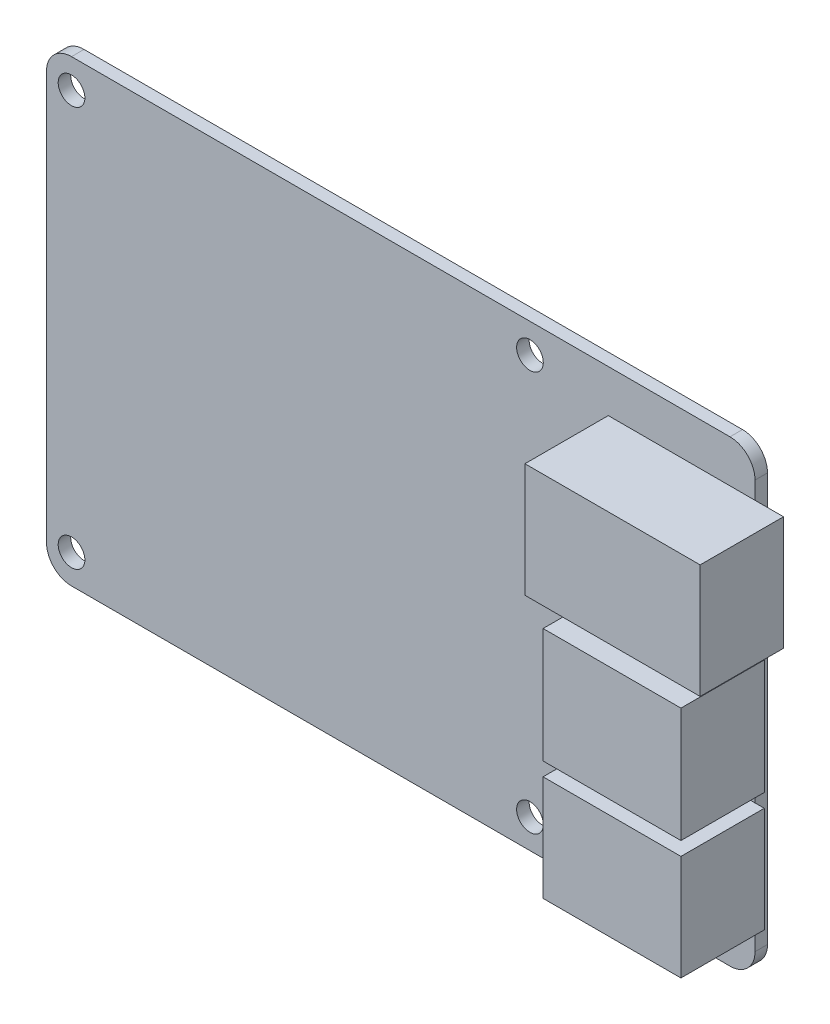
SolidWorks part; units mm, degrees
ref_plane "Front Plane" through (0, 0, 0) normal (0, 0, 1) x (1, 0, 0)
ref_plane "Top Plane" through (0, 0, 0) normal (0, 1, 0) x (1, 0, 0)
ref_plane "Right Plane" through (0, 0, 0) normal (1, 0, 0) x (0, 0, -1)
sketch "Sketch1" plane through (0, 0, 0) normal (0, 0, 1) x (1, 0, 0)
  line L0 (4.3421, -1.9236) -> (89.3421, -1.9236) construction
  line L1 (7.3421, 25.5764) -> (86.3421, 25.5764)
  line L2 (4.3421, 22.5764) -> (4.3421, -26.4236)
  line L3 (7.3421, -29.4236) -> (86.3421, -29.4236)
  line L4 (89.3421, 22.5764) -> (89.3421, -26.4236)
  line L5 (34.8421, 13.4947) -> (34.8421, -15.8686) construction
  line L6 (65.3421, -1.9236) -> (-19.6579, -1.9236) construction
  circle A0 centre (7.3421, 22.0764) radius 1.6
  circle A1 centre (7.3421, -25.9236) radius 1.6
  circle A2 centre (7.3421, 22.0764) radius 1.6
  circle A3 centre (7.3421, -25.9236) radius 1.6
  circle A4 centre (7.3421, 22.0764) radius 1.6
  circle A5 centre (7.3421, -25.9236) radius 1.6
  circle A6 centre (7.3421, 22.0764) radius 1.6
  circle A7 centre (7.3421, -25.9236) radius 1.6
  circle A8 centre (62.3421, -25.9236) radius 1.6
  circle A9 centre (62.3421, 22.0764) radius 1.6
  circle A10 centre (62.3421, -25.9236) radius 1.6
  circle A11 centre (62.3421, 22.0764) radius 1.6
  circle A12 centre (62.3421, -25.9236) radius 1.6
  circle A13 centre (62.3421, 22.0764) radius 1.6
  circle A14 centre (62.3421, -25.9236) radius 1.6
  circle A15 centre (62.3421, 22.0764) radius 1.6
  arc A16 (86.3421, 25.5764) -> (89.3421, 22.5764) centre (86.3421, 22.5764) cw
  arc A17 (86.3421, -29.4236) -> (89.3421, -26.4236) centre (86.3421, -26.4236) ccw
  arc A18 (7.3421, 25.5764) -> (4.3421, 22.5764) centre (7.3421, 22.5764) ccw
  arc A19 (4.3421, -26.4236) -> (7.3421, -29.4236) centre (7.3421, -26.4236) ccw
  point P32 (89.3421, 25.5764)
  point P35 (89.3421, -29.4236)
  point P38 (4.3421, 25.5764)
  dimension "D3" = 24
  dimension "D4" = 3
  dimension "D5" = 27.5
  dimension "D6" = 3
  dimension "D1" = 85
  dimension "D2" = 55
extrude "Boss-Extrude1" add sketch "Sketch1" along normal blind 1.5 contours L4 L1 L2 L3 A1 A0 A8 A9 region at (46.9253, -1.9236, 0)
sketch "Sketch2" plane through (0, 0, 1.5) normal (0, 0, 1) x (1, 0, 0)
  line L1 (71.7387, 20.4772) -> (92.7595, 20.4772)
  line L2 (71.7387, 20.4772) -> (71.7387, 6.8085)
  line L3 (71.7387, 6.8085) -> (92.7595, 6.8085)
  line L4 (92.7595, 20.4772) -> (92.7595, 6.8085)
  line L5 (73.917, 4.445) -> (90.4556, 4.445)
  line L6 (73.917, 4.445) -> (73.917, -9.32)
  line L7 (73.917, -9.32) -> (90.4556, -9.32)
  line L8 (90.4556, 4.445) -> (90.4556, -9.32)
  line L9 (73.917, -10.9636) -> (90.4556, -10.9636)
  line L10 (73.917, -10.9636) -> (73.917, -23.5987)
  line L11 (73.917, -23.5987) -> (90.4556, -23.5987)
  line L12 (90.4556, -10.9636) -> (90.4556, -23.5987)
extrude "Boss-Extrude2" add sketch "Sketch2" along normal blind 10
